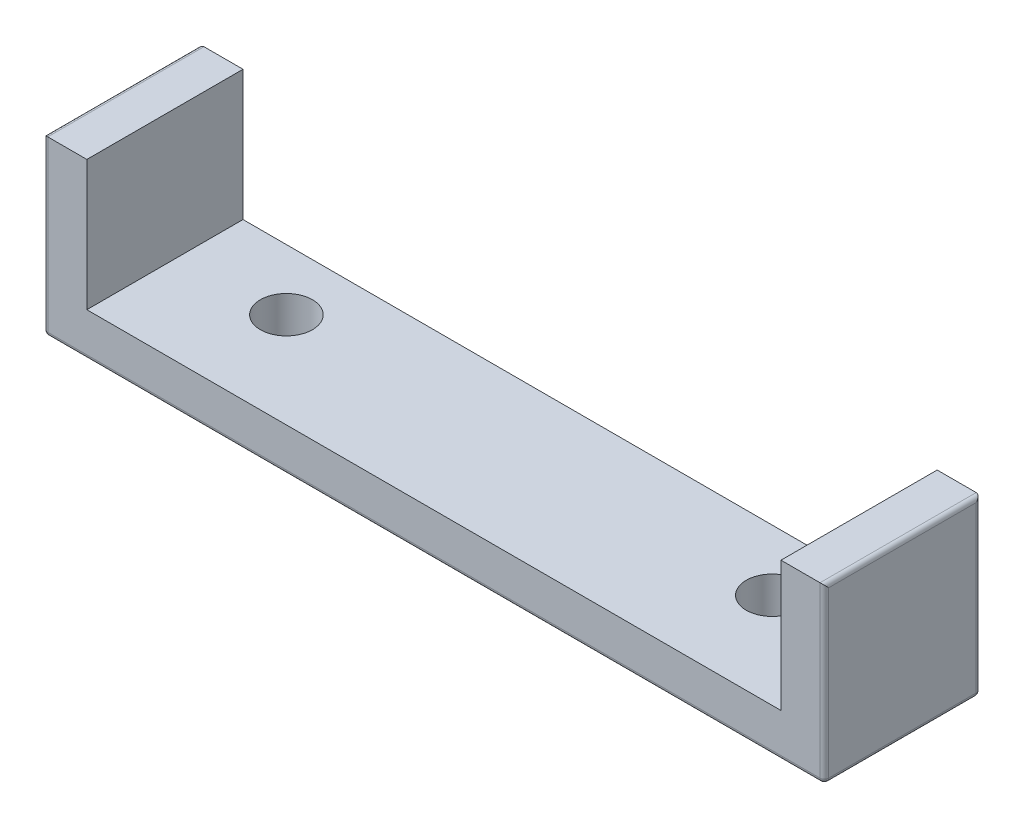
SolidWorks part; units mm, degrees
ref_plane "Front Plane" through (0, 0, 0) normal (0, 0, 1) x (1, 0, 0)
ref_plane "Top Plane" through (0, 0, 0) normal (0, 1, 0) x (1, 0, 0)
ref_plane "Right Plane" through (0, 0, 0) normal (1, 0, 0) x (0, 0, -1)
sketch "Sketch1" plane through (0, 0, 0) normal (0, 1, 0) x (1, 0, 0)
  line L0 (142.5033, 0) -> (142.5033, -18)
  line L1 (0, 0) -> (205, 0)
  line L2 (0, 0) -> (0, -18)
  line L3 (0, -18) -> (205, -18)
  line L4 (205, 0) -> (205, -18)
  line L5 (62.5033, 0) -> (62.5033, -18)
  line L6 (57.5033, 0) -> (57.5033, -18)
  line L7 (147.5033, 0) -> (147.5033, -18)
  circle A0 centre (4.99, -8) radius 3
  circle A1 centre (36.99, -8) radius 3
  circle A2 centre (74.5033, -7) radius 3
  circle A3 centre (130.5033, -7) radius 3
  circle A4 centre (168.0133, -8) radius 3
  circle A5 centre (200.0133, -8) radius 3
  dimension "D5" = 6
  dimension "D6" = 6
  dimension "D1" = 205
  dimension "D2" = 18
  dimension "D3" = 8
  dimension "D4" = 7
  dimension "D7" = 32
  dimension "D8" = 56
  dimension "D9" = 32
  dimension "D10" = 37.5133
  dimension "D11" = 37.51
  dimension "D12" = 4.99
  dimension "D13" = 4.9867
  dimension "D14" = 80
  dimension "D15" = 12
  dimension "D16" = 5
  dimension "D17" = 5
extrude "Boss-Extrude1" add sketch "Sketch1" along normal blind 5 contours L1 L5 L3 L0 A3 A2 region at (102.5033, 0, 9.0818)
extrude "Boss-Extrude2" add sketch "Sketch1<6>" along normal blind 20 contours L1 L6 L3 L5 | L7 L1 L0 L3 region at (145.0033, 0, 9) region at (60.0033, 0, 9)
sketch "Sketch1<6>" plane through (0, 0, 0) normal (0, 1, 0) x (1, 0, 0) same geometry as "Sketch1"
fillet "Fillet1" radius 0.5 12 edges at (57.5033, 10, 0) (57.5033, 20, 9) (57.5033, 10, 18) (57.5033, 0, 9) (102.5033, 0, 18) (102.5033, 0, 0) (74.5033, 0, 10) (130.5033, 0, 10) (147.5033, 10, 18) (147.5033, 20, 9) (147.5033, 10, 0) (147.5033, 0, 9)
